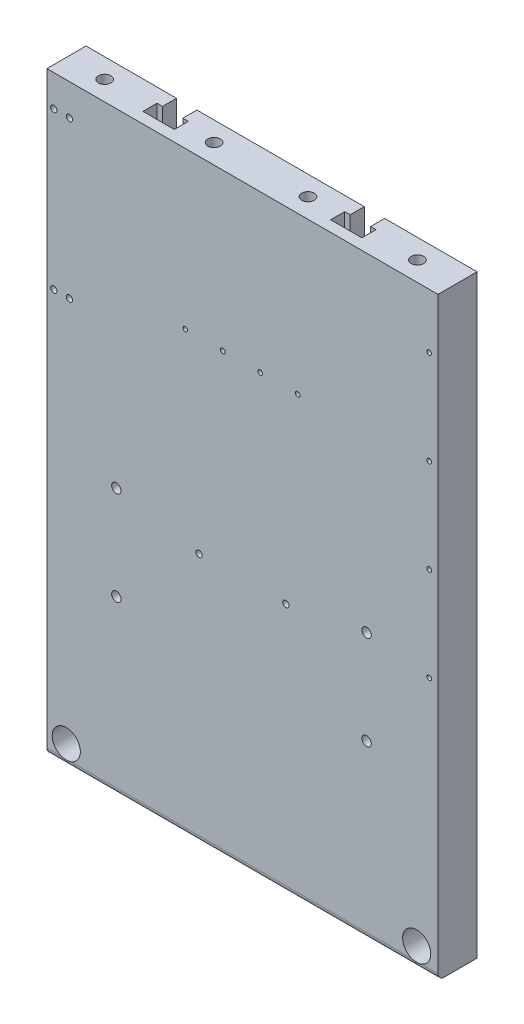
SolidWorks part; units mm, degrees
ref_plane "前视基准面" through (0, 0, 0) normal (0, 0, 1) x (1, 0, 0)
ref_plane "上视基准面" through (0, 0, 0) normal (0, 1, 0) x (1, 0, 0)
ref_plane "右视基准面" through (0, 0, 0) normal (1, 0, 0) x (0, 0, -1)
other "Configuration Table"
sketch "草图1" plane through (0, 0, 0) normal (0, 0, 1) x (1, 0, 0)
  line L0 (0.6138, 380.0763) -> (5, 380.0763)
  line L1 (0.6138, 0.0763) -> (250.6138, 0.0763)
  line L2 (0.6138, 0.0763) -> (0.6138, 380.0763)
  line L3 (0.6138, 380.0763) -> (250.6138, 380.0763)
  line L4 (250.6138, 0.0763) -> (250.6138, 380.0763)
  line L5 (5, 380.0763) -> (5, 360)
  circle A0 centre (13, 12.5) radius 9
  circle A1 centre (237, 12.5) radius 9
  circle A2 centre (5, 360) radius 2
  circle A3 centre (5, 260) radius 2
  circle A4 centre (15, 360) radius 2
  circle A5 centre (15, 260) radius 2
  circle A6 centre (89, 280) radius 1.5
  circle A7 centre (113, 280) radius 1.5
  circle A8 centre (137, 280) radius 1.5
  circle A9 centre (161, 280) radius 1.5
  circle A10 centre (45, 110) radius 3
  circle A11 centre (45, 170) radius 3
  circle A12 centre (205, 170) radius 3
  circle A13 centre (205, 110) radius 3
  circle A14 centre (245, 345) radius 1.5
  circle A15 centre (245, 285) radius 1.5
  circle A16 centre (245, 225) radius 1.5
  circle A17 centre (245, 165) radius 1.5
sketch "草图2" plane through (0, 0, 0) normal (0, 0, 1) x (1, 0, 0)
extrude "凸台-拉伸3" add sketch "草图1" along normal blind 25 contours A2 L0 L2 L1 L4 L3 A17 A16 A15 A14 A13 A12 A11 A10 A9 A8 A7 A6 A5 A4 A3 A1 A0 region at (125.6439, 190.9847, 0)
cosmetic thread "装饰螺纹线25" parameters "D2"=8
cosmetic thread "装饰螺纹线26" parameters "D2"=8
cosmetic thread "装饰螺纹线27" parameters "D2"=8
cosmetic thread "装饰螺纹线28" parameters "D2"=8
cosmetic thread "装饰螺纹线35" parameters "D2"=4
cosmetic thread "装饰螺纹线36" parameters "D2"=4
cosmetic thread "装饰螺纹线37" parameters "D2"=4
cosmetic thread "装饰螺纹线38" parameters "D2"=4
cosmetic thread "装饰螺纹线39" parameters "D2"=5
cosmetic thread "装饰螺纹线40" parameters "D2"=5
cosmetic thread "装饰螺纹线41" parameters "D2"=5
cosmetic thread "装饰螺纹线42" parameters "D2"=5
cosmetic thread "装饰螺纹线43" parameters "D2"=4
cosmetic thread "装饰螺纹线44" parameters "D2"=4
cosmetic thread "装饰螺纹线45" parameters "D2"=4
cosmetic thread "装饰螺纹线46" parameters "D2"=4
sketch "草图3" plane through (0, 380.0763, 0) normal (0, 1, 0) x (1, 0, 0)
  line L0 (71.5, 0) -> (71.5, -9)
  line L2 (58.5, 0) -> (58.5, -9)
  line L3 (71.5, -9) -> (75, -9)
  line L4 (55, -9) -> (58.5, -9)
  line L5 (55, -9) -> (55, -18)
  line L6 (75, -9) -> (75, -18)
  line L7 (55, -18) -> (75, -18)
  line L8 (178.5, 0) -> (178.5, -9)
  line L9 (191.5, 0) -> (191.5, -9)
  line L10 (191.5, -9) -> (195, -9)
  line L11 (178.5, -9) -> (175, -9)
  line L12 (175, -9) -> (175, -18)
  line L13 (175, -18) -> (195, -18)
  line L14 (195, -18) -> (195, -9)
  circle A1 centre (155, -12.5) radius 4
  circle A2 centre (95, -12.5) radius 4
  circle A3 centre (225, -12.5) radius 4
  circle A4 centre (25, -12.5) radius 4
  line M15 (250.6138, 0) -> (0.6138, 0)
extrude "切除-拉伸1" cut sketch "草图3" against normal blind 416 contours L5 L7 L6 L3 L0 L2 L4 M15 | L13 L14 L10 L9 L8 L11 L12 M15 region at (185, 380.0763, 9.9545) region at (65, 380.0763, 9.9545)
extrude "切除-拉伸2" cut sketch "草图3<4>" against normal blind 55 contours A2 | A1 | A3 | A4 region at (155, 380.0763, 12.5) region at (95, 380.0763, 12.5) region at (225, 380.0763, 12.5)
sketch "草图3<4>" plane through (0, 380.0763, 0) normal (0, 1, 0) x (1, 0, 0) same geometry as "草图3"
cosmetic thread "装饰螺纹线31" parameters "D2"=10
cosmetic thread "装饰螺纹线32" parameters "D2"=10
cosmetic thread "装饰螺纹线33" parameters "D2"=10
cosmetic thread "装饰螺纹线34" parameters "D2"=10
sketch "草图5" plane through (0, 0, 0) normal (0, 0, -1) x (-1, 0, 0)
  line L1 (-162.6237, 288.9406) -> (-86.2052, 288.9406)
  line L2 (-162.6237, 288.9406) -> (-162.6237, 270.7784)
  line L3 (-162.6237, 270.7784) -> (-86.2052, 270.7784)
  line L4 (-86.2052, 288.9406) -> (-86.2052, 270.7784)
extrude "凸台-拉伸4" add sketch "草图5" against normal blind 12
sketch "草图6" plane through (0, 0, 0) normal (0, 0, -1) x (-1, 0, 0)
  line L1 (-249.3176, 351.9945) -> (-239.3798, 351.9945)
  line L2 (-249.3176, 351.9945) -> (-249.3176, 154.2658)
  line L3 (-249.3176, 154.2658) -> (-239.3798, 154.2658)
  line L4 (-239.3798, 351.9945) -> (-239.3798, 154.2658)
extrude "凸台-拉伸5" add sketch "草图6" against normal blind 12
sketch "草图7" plane through (0, 0, 0) normal (0, 0, -1) x (-1, 0, 0)
  line L0 (-0.6138, 0.0763) -> (-0.6138, 380.0763) construction
  line L1 (-21.6747, 366.3184) -> (-0.6138, 366.3184)
  line L2 (-21.6747, 366.3184) -> (-21.6747, 254.5838)
  line L3 (-21.6747, 254.5838) -> (-0.6138, 254.5838)
  line L4 (-0.6138, 366.3184) -> (-0.6138, 254.5838)
extrude "凸台-拉伸6" add sketch "草图7" against normal blind 12
sketch "草图8" plane through (0, 0, 0) normal (0, 0, -1) x (-1, 0, 0)
  line L1 (-212.3129, 176.883) -> (-196.5494, 176.883)
  line L2 (-212.3129, 176.883) -> (-212.3129, 100.4644)
  line L3 (-212.3129, 100.4644) -> (-196.5494, 100.4644)
  line L4 (-196.5494, 176.883) -> (-196.5494, 100.4644)
extrude "凸台-拉伸7" add sketch "草图8" against normal blind 5
sketch "草图9" plane through (0, 0, 0) normal (0, 0, -1) x (-1, 0, 0)
  line L1 (-50.9087, 177.2256) -> (-39.9428, 177.2256)
  line L2 (-50.9087, 177.2256) -> (-50.9087, 101.8352)
  line L3 (-50.9087, 101.8352) -> (-39.9428, 101.8352)
  line L4 (-39.9428, 177.2256) -> (-39.9428, 101.8352)
extrude "凸台-拉伸8" add sketch "草图9" against normal blind 5
sketch "草图10" plane through (0, 0, 0) normal (0, 0, -1) x (-1, 0, 0)
  line L0 (-125, 0.0763) -> (-125, 380.0763)
  line L1 (-247.5994, 28.6221) -> (-226.2946, 28.6221)
  line L2 (-247.5994, 28.6221) -> (-247.5994, 1.6251)
  line L3 (-247.5994, 1.6251) -> (-226.2946, 1.6251)
  line L4 (-226.2946, 28.6221) -> (-226.2946, 1.6251)
  line L5 (-71.5, 0.0763) -> (-178.5, 0.0763) construction
  line L6 (-71.5, 380.0763) -> (-178.5, 380.0763) construction
  line L7 (-2.4006, 28.6221) -> (-2.4006, 1.6251)
  line L8 (-2.4006, 1.6251) -> (-23.7054, 1.6251)
  line L9 (-23.7054, 28.6221) -> (-23.7054, 1.6251)
  line L10 (-2.4006, 28.6221) -> (-23.7054, 28.6221)
  circle A2 centre (-237, 12.5) radius 6
  circle A3 centre (-13, 12.5) radius 6
extrude "凸台-拉伸11" add sketch "草图10" against normal blind 11 contours A2 | L7 L10 L9 L8 A3 region at (236.947, 28.2782, 0) region at (2.7445, 15.1236, 0)
fillet "圆角1" radius 4 1 edges at (125.6138, 0.0763, 25)
sketch "草图11" plane through (0, 0, 25) normal (0, 0, 1) x (1, 0, 0)
  circle A0 centre (153.3638, 160.0763) radius 2
  circle A1 centre (97.8638, 160.0763) radius 2
extrude "切除-拉伸3" cut sketch "草图11" against normal blind 13
cosmetic thread "装饰螺纹线29" parameters "D2"=5
cosmetic thread "装饰螺纹线30" parameters "D2"=5
